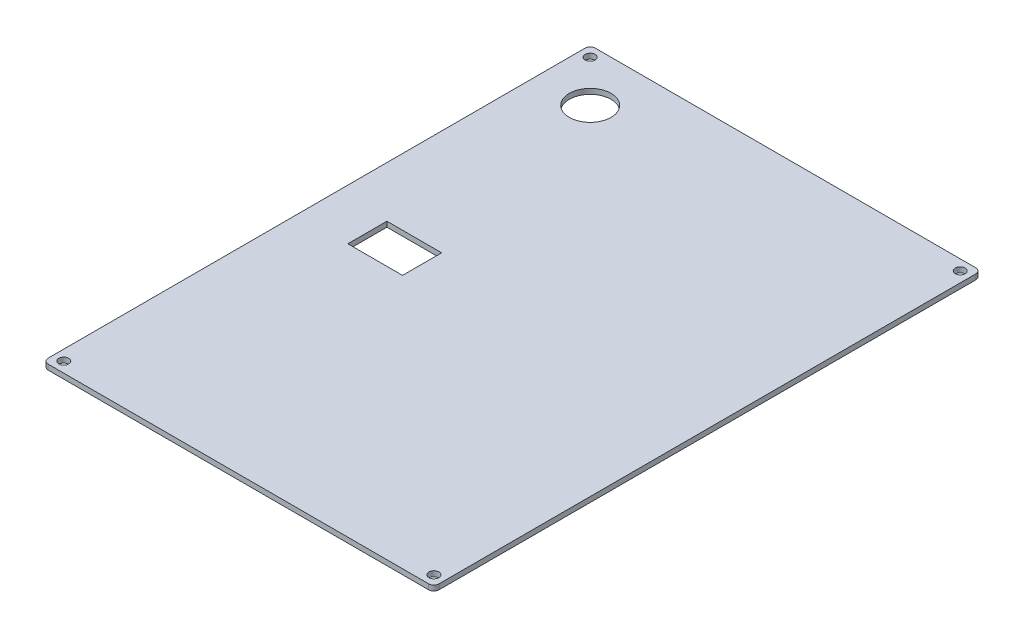
SolidWorks part; units mm, degrees
ref_plane "Front Plane" through (0, 0, 0) normal (0, 0, 1) x (1, 0, 0)
ref_plane "Top Plane" through (0, 0, 0) normal (0, 1, 0) x (1, 0, 0)
ref_plane "Right Plane" through (0, 0, 0) normal (1, 0, 0) x (0, 0, -1)
sketch "Sketch1" plane through (0, 0, 0) normal (0, 1, 0) x (1, 0, 0)
  line L1 (0, 0) -> (150, 0)
  line L2 (0, 0) -> (0, 210)
  line L3 (0, 210) -> (150, 210)
  line L4 (150, 0) -> (150, 210)
  dimension "D1" = 150
  dimension "D2" = 210
extrude "Boss-Extrude1" add sketch "Sketch1" along normal blind 2
sketch "Sketch2" plane through (0, 2, 0) normal (0, 1, 0) x (1, 0, 0)
  line L0 (4, 210) -> (4, 206) construction
  line L1 (150, 210) -> (0, 210) construction
  line L2 (4, 206) -> (0, 206) construction
  line L3 (0, 210) -> (0, 0) construction
  line L4 (75, 210) -> (75, 0) construction
  line L5 (0, 0) -> (150, 0) construction
  line L6 (0, 105) -> (150, 105) construction
  line L7 (150, 0) -> (150, 210) construction
  line L8 (146, 206) -> (150, 206) construction
  line L9 (146, 210) -> (146, 206) construction
  line L10 (146, 0) -> (146, 4) construction
  line L11 (146, 4) -> (150, 4) construction
  line L12 (4, 4) -> (0, 4) construction
  line L13 (4, 0) -> (4, 4) construction
  line L14 (140, 10) -> (140, 0) construction
  line L15 (140, 10) -> (150, 10) construction
  line L16 (0, 190) -> (20, 190) construction
  line L17 (20, 190) -> (20, 210) construction
  circle A0 centre (4, 206) radius 1.9
  circle A1 centre (146, 206) radius 1.9
  circle A2 centre (146, 4) radius 1.9
  circle A3 centre (4, 4) radius 1.9
  circle A5 centre (20, 190) radius 8
  dimension "D2" = 3.8
  dimension "D8" = 16
  dimension "D1" = 4
  dimension "D3" = 10
  dimension "D4" = 10
  dimension "D6" = 20
  dimension "D7" = 20
extrude "Cut-Extrude1" cut sketch "Sketch2" against normal blind 10
fillet "Fillet1" radius 2 4 edges at (0, 1, 0) (150, 1, 0) (150, 1, -210) (0, 1, -210)
sketch "Sketch3" plane through (0, 2, 0) normal (0, 1, 0) x (1, 0, 0)
  line L0 (0, 105) -> (30, 105) construction
  line L1 (0, 208) -> (0, 2) construction
  line L3 (19.5, 97.5) -> (40.5, 97.5)
  line L4 (19.5, 97.5) -> (19.5, 112.5)
  line L5 (19.5, 112.5) -> (40.5, 112.5)
  line L6 (40.5, 97.5) -> (40.5, 112.5)
  line L7 (19.5, 97.5) -> (40.5, 112.5) construction
  line L8 (19.5, 112.5) -> (40.5, 97.5) construction
  dimension "D1" = 30
  dimension "D2" = 21
  dimension "D3" = 15
extrude "Cut-Extrude2" cut sketch "Sketch3" against normal blind 10
